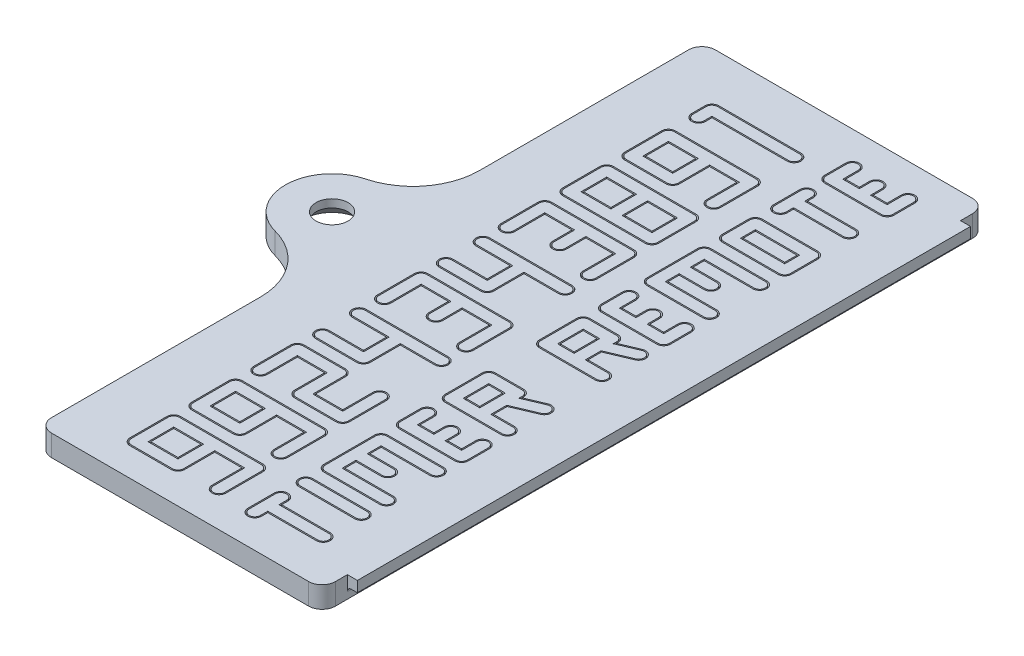
SolidWorks part; units mm, degrees
ref_plane "Front Plane" through (0, 0, 0) normal (0, 0, 1) x (1, 0, 0)
ref_plane "Top Plane" through (0, 0, 0) normal (0, 1, 0) x (1, 0, 0)
ref_plane "Right Plane" through (0, 0, 0) normal (1, 0, 0) x (0, 0, -1)
sketch "Door Plate 1.6 + screw ear (R5 / R3.5) Sketch" plane through (0, 0, 0) normal (0, 1, 0) x (1, 0, 0)
  line L0 (9.35, 15.1) -> (30.65, 15.1)
  line L1 (30.65, 15.1) -> (30.65, 64.9)
  line L2 (30.65, 64.9) -> (9.35, 64.9)
  line L3 (9.35, 64.9) -> (9.35, 48.2236)
  line L4 (9.35, 31.7764) -> (9.35, 15.1)
  arc A0 (9.35, 31.7764) -> (5.6147, 36.6138) centre (4.35, 31.7764) ccw
  arc A1 (5.6147, 36.6138) -> (5.6147, 43.3862) centre (6.5, 40) cw
  arc A2 (5.6147, 43.3862) -> (9.35, 48.2236) centre (4.35, 48.2236) ccw
extrude "Door Plate 1.6 + screw ear (R5 / R3.5)" add sketch "Door Plate 1.6 + screw ear (R5 / R3.5) Sketch" along normal blind 1.6
ref_plane "Hook Flange Plane y0.8" through (0, 0.8, 0) normal (0, 1, 0) x (1, 0, 0)
sketch "Hook Flange 0.75 x 0.8 (inner-face plane) Sketch" plane through (0, 0.8, 0) normal (0, 1, 0) x (1, 0, 0)
  line L0 (30.5, 17) -> (31.4, 17)
  line L1 (31.4, 17) -> (31.4, 63)
  line L2 (31.4, 63) -> (30.5, 63)
  line L3 (30.5, 63) -> (30.5, 17)
extrude "Hook Flange 0.75 x 0.8 (inner-face plane)" add sketch "Hook Flange 0.75 x 0.8 (inner-face plane) Sketch" along normal blind 0.8
sketch "Screw Hole 2.4 (free) Sketch" plane through (0, 0, 0) normal (0, 1, 0) x (1, 0, 0)
  circle A0 centre (6.5, 40) radius 1.2
extrude "Screw Hole 2.4 (free)" cut sketch "Screw Hole 2.4 (free) Sketch" along normal through all
chamfer "Screw CSK 90deg (M2)" distance 1 angle 45 1 edges at (6.5, 0, -38.8)
fillet "Door Corners R1 (print)" radius 1 4 edges at (9.35, 0.8, -64.9) (30.65, 0.8, -64.9) (30.65, 0.8, -15.1) (9.35, 0.8, -15.1)
fillet "Hook Flange Root Fillet R0.3" radius 0.3 1 edges at (30.65, 0.8, -40)
ref_plane "Number Plane y1.6" through (0, 1.6, 0) normal (0, 1, 0) x (1, 0, 0)
sketch "Door Text Slits 9924343891 + TIMER REMOTE (0.84 stroke) Sketch" plane through (0, 1.6, 0) normal (0, 1, 0) x (1, 0, 0)
  line L0 (17.2, 17.22) -> (14.12, 17.22)
  line L1 (13.6, 17.74) -> (13.6, 20.5)
  line L2 (14.12, 21.02) -> (20.28, 21.02)
  line L3 (20.8, 20.5) -> (20.8, 17.74)
  line L4 (19.76, 17.74) -> (19.76, 19.98)
  line L5 (19.76, 19.98) -> (17.72, 19.98)
  line L6 (17.72, 19.98) -> (17.72, 17.74)
  line L7 (13.7, 20.5) -> (13.7, 17.74)
  line L8 (14.12, 17.32) -> (17.2, 17.32)
  line L9 (17.62, 17.74) -> (17.62, 20.08)
  line L10 (17.62, 20.08) -> (19.86, 20.08)
  line L11 (19.86, 20.08) -> (19.86, 17.74)
  line L12 (20.7, 17.74) -> (20.7, 20.5)
  line L13 (20.28, 20.92) -> (14.12, 20.92)
  line L14 (17.2, 21.86) -> (14.12, 21.86)
  line L15 (13.6, 22.38) -> (13.6, 25.14)
  line L16 (14.12, 25.66) -> (20.28, 25.66)
  line L17 (20.8, 25.14) -> (20.8, 22.38)
  line L18 (19.76, 22.38) -> (19.76, 24.62)
  line L19 (19.76, 24.62) -> (17.72, 24.62)
  line L20 (17.72, 24.62) -> (17.72, 22.38)
  line L21 (13.7, 25.14) -> (13.7, 22.38)
  line L22 (14.12, 21.96) -> (17.2, 21.96)
  line L23 (17.62, 22.38) -> (17.62, 24.72)
  line L24 (17.62, 24.72) -> (19.86, 24.72)
  line L25 (19.86, 24.72) -> (19.86, 22.38)
  line L26 (20.7, 22.38) -> (20.7, 25.14)
  line L27 (20.28, 25.56) -> (14.12, 25.56)
  line L28 (20.8, 29.78) -> (20.8, 27.02)
  line L29 (20.28, 26.5) -> (17.2, 26.5)
  line L30 (16.68, 27.02) -> (16.68, 29.26)
  line L31 (16.68, 29.26) -> (14.64, 29.26)
  line L32 (14.64, 29.26) -> (14.64, 27.02)
  line L33 (13.6, 27.02) -> (13.6, 29.78)
  line L34 (14.12, 30.3) -> (17.2, 30.3)
  line L35 (17.72, 29.78) -> (17.72, 27.54)
  line L36 (17.72, 27.54) -> (19.76, 27.54)
  line L37 (19.76, 27.54) -> (19.76, 29.78)
  line L38 (14.54, 29.36) -> (14.54, 27.02)
  line L39 (13.7, 27.02) -> (13.7, 29.78)
  line L40 (14.12, 30.2) -> (17.2, 30.2)
  line L41 (17.62, 29.78) -> (17.62, 27.44)
  line L42 (17.62, 27.44) -> (19.86, 27.44)
  line L43 (19.86, 27.44) -> (19.86, 29.78)
  line L44 (20.7, 29.78) -> (20.7, 27.02)
  line L45 (20.28, 26.6) -> (17.2, 26.6)
  line L46 (16.78, 27.02) -> (16.78, 29.36)
  line L47 (16.78, 29.36) -> (14.54, 29.36)
  line L48 (20.28, 33.9) -> (17.72, 33.9)
  line L49 (17.72, 33.9) -> (17.72, 31.66)
  line L50 (17.2, 31.14) -> (14.12, 31.14)
  line L51 (14.12, 32.18) -> (16.68, 32.18)
  line L52 (16.68, 32.18) -> (16.68, 33.9)
  line L53 (16.68, 33.9) -> (14.12, 33.9)
  line L54 (14.12, 34.94) -> (20.28, 34.94)
  line L55 (17.62, 31.66) -> (17.62, 34)
  line L56 (17.62, 34) -> (20.28, 34)
  line L57 (20.28, 34.84) -> (14.12, 34.84)
  line L58 (14.12, 34) -> (16.78, 34)
  line L59 (16.78, 34) -> (16.78, 32.08)
  line L60 (16.78, 32.08) -> (14.12, 32.08)
  line L61 (14.12, 31.24) -> (17.2, 31.24)
  line L62 (19.76, 36.3) -> (19.76, 38.54)
  line L63 (19.76, 38.54) -> (17.72, 38.54)
  line L64 (17.72, 38.54) -> (17.72, 37.1)
  line L65 (16.68, 37.1) -> (16.68, 38.54)
  line L66 (16.68, 38.54) -> (14.64, 38.54)
  line L67 (14.64, 38.54) -> (14.64, 36.3)
  line L68 (13.6, 36.3) -> (13.6, 39.06)
  line L69 (14.12, 39.58) -> (20.28, 39.58)
  line L70 (20.8, 39.06) -> (20.8, 36.3)
  line L71 (13.7, 36.3) -> (13.7, 39.06)
  line L72 (14.12, 39.48) -> (20.28, 39.48)
  line L73 (20.7, 39.06) -> (20.7, 36.3)
  line L74 (19.86, 36.3) -> (19.86, 38.64)
  line L75 (19.86, 38.64) -> (17.62, 38.64)
  line L76 (17.62, 38.64) -> (17.62, 37.1)
  line L77 (16.78, 37.1) -> (16.78, 38.64)
  line L78 (16.78, 38.64) -> (14.54, 38.64)
  line L79 (14.54, 38.64) -> (14.54, 36.3)
  line L80 (20.28, 43.18) -> (17.72, 43.18)
  line L81 (17.72, 43.18) -> (17.72, 40.94)
  line L82 (17.2, 40.42) -> (14.12, 40.42)
  line L83 (14.12, 41.46) -> (16.68, 41.46)
  line L84 (16.68, 41.46) -> (16.68, 43.18)
  line L85 (16.68, 43.18) -> (14.12, 43.18)
  line L86 (14.12, 44.22) -> (20.28, 44.22)
  line L87 (17.62, 40.94) -> (17.62, 43.28)
  line L88 (17.62, 43.28) -> (20.28, 43.28)
  line L89 (20.28, 44.12) -> (14.12, 44.12)
  line L90 (14.12, 43.28) -> (16.78, 43.28)
  line L91 (16.78, 43.28) -> (16.78, 41.36)
  line L92 (16.78, 41.36) -> (14.12, 41.36)
  line L93 (14.12, 40.52) -> (17.2, 40.52)
  line L94 (19.76, 45.58) -> (19.76, 47.82)
  line L95 (19.76, 47.82) -> (17.72, 47.82)
  line L96 (17.72, 47.82) -> (17.72, 46.38)
  line L97 (16.68, 46.38) -> (16.68, 47.82)
  line L98 (16.68, 47.82) -> (14.64, 47.82)
  line L99 (14.64, 47.82) -> (14.64, 45.58)
  line L100 (13.6, 45.58) -> (13.6, 48.34)
  line L101 (14.12, 48.86) -> (20.28, 48.86)
  line L102 (20.8, 48.34) -> (20.8, 45.58)
  line L103 (13.7, 45.58) -> (13.7, 48.34)
  line L104 (14.12, 48.76) -> (20.28, 48.76)
  line L105 (20.7, 48.34) -> (20.7, 45.58)
  line L106 (19.86, 45.58) -> (19.86, 47.92)
  line L107 (19.86, 47.92) -> (17.62, 47.92)
  line L108 (17.62, 47.92) -> (17.62, 46.38)
  line L109 (16.78, 46.38) -> (16.78, 47.92)
  line L110 (16.78, 47.92) -> (14.54, 47.92)
  line L111 (14.54, 47.92) -> (14.54, 45.58)
  line L112 (20.8, 52.98) -> (20.8, 50.22)
  line L113 (20.28, 49.7) -> (14.12, 49.7)
  line L114 (13.6, 50.22) -> (13.6, 52.98)
  line L115 (14.12, 53.5) -> (20.28, 53.5)
  line L116 (20.7, 50.22) -> (20.7, 52.98)
  line L117 (20.28, 53.4) -> (14.12, 53.4)
  line L118 (13.7, 52.98) -> (13.7, 50.22)
  line L119 (14.12, 49.8) -> (20.28, 49.8)
  line L120 (17.2, 54.34) -> (14.12, 54.34)
  line L121 (13.6, 54.86) -> (13.6, 57.62)
  line L122 (14.12, 58.14) -> (20.28, 58.14)
  line L123 (20.8, 57.62) -> (20.8, 54.86)
  line L124 (19.76, 54.86) -> (19.76, 57.1)
  line L125 (19.76, 57.1) -> (17.72, 57.1)
  line L126 (17.72, 57.1) -> (17.72, 54.86)
  line L127 (13.7, 57.62) -> (13.7, 54.86)
  line L128 (14.12, 54.44) -> (17.2, 54.44)
  line L129 (17.62, 54.86) -> (17.62, 57.2)
  line L130 (17.62, 57.2) -> (19.86, 57.2)
  line L131 (19.86, 57.2) -> (19.86, 54.86)
  line L132 (20.7, 54.86) -> (20.7, 57.62)
  line L133 (20.28, 58.04) -> (14.12, 58.04)
  line L134 (20.28, 60.36) -> (14.64, 60.36)
  line L135 (14.64, 60.36) -> (14.64, 59.88)
  line L136 (13.6, 59.88) -> (13.6, 60.88)
  line L137 (14.12, 61.4) -> (20.28, 61.4)
  line L138 (14.54, 60.46) -> (14.54, 59.88)
  line L139 (13.7, 59.88) -> (13.7, 60.88)
  line L140 (14.12, 61.3) -> (20.28, 61.3)
  line L141 (20.28, 60.46) -> (14.54, 60.46)
  line L142 (23.64, 19.08) -> (27.28, 19.08)
  line L143 (27.28, 18.04) -> (23.64, 18.04)
  line L144 (23.64, 18.04) -> (23.64, 17.58)
  line L145 (22.6, 17.58) -> (22.6, 19.54)
  line L146 (23.64, 19.54) -> (23.64, 19.08)
  line L147 (22.7, 17.58) -> (22.7, 19.54)
  line L148 (23.54, 19.54) -> (23.54, 18.98)
  line L149 (23.54, 18.98) -> (27.28, 18.98)
  line L150 (27.28, 18.14) -> (23.54, 18.14)
  line L151 (23.54, 18.14) -> (23.54, 17.58)
  line L152 (27.28, 20.9) -> (23.12, 20.9)
  line L153 (23.12, 21.94) -> (27.28, 21.94)
  line L154 (27.28, 21) -> (23.12, 21)
  line L155 (23.12, 21.84) -> (27.28, 21.84)
  line L156 (27.28, 26.54) -> (23.64, 26.54)
  line L157 (23.64, 26.54) -> (23.64, 25.7)
  line L158 (23.64, 25.7) -> (25.5, 25.7)
  line L159 (25.5, 24.66) -> (23.64, 24.66)
  line L160 (23.64, 24.66) -> (23.64, 23.82)
  line L161 (23.64, 23.82) -> (27.28, 23.82)
  line L162 (27.28, 22.78) -> (23.12, 22.78)
  line L163 (22.6, 23.3) -> (22.6, 27.06)
  line L164 (23.12, 27.58) -> (27.28, 27.58)
  line L165 (27.28, 22.88) -> (23.12, 22.88)
  line L166 (22.7, 23.3) -> (22.7, 27.06)
  line L167 (23.12, 27.48) -> (27.28, 27.48)
  line L168 (27.28, 26.64) -> (23.54, 26.64)
  line L169 (23.54, 26.64) -> (23.54, 25.6)
  line L170 (23.54, 25.6) -> (25.5, 25.6)
  line L171 (25.5, 24.76) -> (23.54, 24.76)
  line L172 (23.54, 24.76) -> (23.54, 23.72)
  line L173 (23.54, 23.72) -> (27.28, 23.72)
  line L174 (26.76, 29.46) -> (26.76, 30.5)
  line L175 (27.8, 30.5) -> (27.8, 28.94)
  line L176 (27.28, 28.42) -> (23.12, 28.42)
  line L177 (22.6, 28.94) -> (22.6, 30.5)
  line L178 (23.64, 30.5) -> (23.64, 29.46)
  line L179 (23.64, 29.46) -> (24.68, 29.46)
  line L180 (24.68, 29.46) -> (24.68, 30.2)
  line L181 (25.72, 30.2) -> (25.72, 29.46)
  line L182 (25.72, 29.46) -> (26.76, 29.46)
  line L183 (23.12, 28.52) -> (27.28, 28.52)
  line L184 (27.7, 28.94) -> (27.7, 30.5)
  line L185 (26.86, 30.5) -> (26.86, 29.36)
  line L186 (26.86, 29.36) -> (25.62, 29.36)
  line L187 (25.62, 29.36) -> (25.62, 30.2)
  line L188 (24.78, 30.2) -> (24.78, 29.36)
  line L189 (24.78, 29.36) -> (23.54, 29.36)
  line L190 (23.54, 29.36) -> (23.54, 30.5)
  line L191 (22.7, 30.5) -> (22.7, 28.94)
  line L192 (25.72, 35.14) -> (25.72, 35.0446)
  line L193 (25.72, 35.0446) -> (27.0774, 35.6189)
  line L194 (27.4826, 34.6611) -> (25.72, 33.9154)
  line L195 (25.72, 33.9154) -> (25.72, 32.9)
  line L196 (25.72, 32.9) -> (27.28, 32.9)
  line L197 (27.28, 31.86) -> (23.12, 31.86)
  line L198 (22.6, 32.38) -> (22.6, 35.14)
  line L199 (23.12, 35.66) -> (25.2, 35.66)
  line L200 (27.28, 31.96) -> (23.12, 31.96)
  line L201 (22.7, 32.38) -> (22.7, 35.14)
  line L202 (23.12, 35.56) -> (25.2, 35.56)
  line L203 (25.62, 35.14) -> (25.62, 34.8937)
  line L204 (25.62, 34.8937) -> (27.1164, 35.5268)
  line L205 (27.4436, 34.7532) -> (25.62, 33.9817)
  line L206 (25.62, 33.9817) -> (25.62, 32.8)
  line L207 (25.62, 32.8) -> (27.28, 32.8)
  line L208 (25.72, 42.22) -> (25.72, 42.1246)
  line L209 (25.72, 42.1246) -> (27.0774, 42.6989)
  line L210 (27.4826, 41.7411) -> (25.72, 40.9954)
  line L211 (25.72, 40.9954) -> (25.72, 39.98)
  line L212 (25.72, 39.98) -> (27.28, 39.98)
  line L213 (27.28, 38.94) -> (23.12, 38.94)
  line L214 (22.6, 39.46) -> (22.6, 42.22)
  line L215 (23.12, 42.74) -> (25.2, 42.74)
  line L216 (27.28, 39.04) -> (23.12, 39.04)
  line L217 (22.7, 39.46) -> (22.7, 42.22)
  line L218 (23.12, 42.64) -> (25.2, 42.64)
  line L219 (25.62, 42.22) -> (25.62, 41.9737)
  line L220 (25.62, 41.9737) -> (27.1164, 42.6068)
  line L221 (27.4436, 41.8332) -> (25.62, 41.0617)
  line L222 (25.62, 41.0617) -> (25.62, 39.88)
  line L223 (25.62, 39.88) -> (27.28, 39.88)
  line L224 (26.76, 44.62) -> (26.76, 45.66)
  line L225 (27.8, 45.66) -> (27.8, 44.1)
  line L226 (27.28, 43.58) -> (23.12, 43.58)
  line L227 (22.6, 44.1) -> (22.6, 45.66)
  line L228 (23.64, 45.66) -> (23.64, 44.62)
  line L229 (23.64, 44.62) -> (24.68, 44.62)
  line L230 (24.68, 44.62) -> (24.68, 45.36)
  line L231 (25.72, 45.36) -> (25.72, 44.62)
  line L232 (25.72, 44.62) -> (26.76, 44.62)
  line L233 (23.12, 43.68) -> (27.28, 43.68)
  line L234 (27.7, 44.1) -> (27.7, 45.66)
  line L235 (26.86, 45.66) -> (26.86, 44.52)
  line L236 (26.86, 44.52) -> (25.62, 44.52)
  line L237 (25.62, 44.52) -> (25.62, 45.36)
  line L238 (24.78, 45.36) -> (24.78, 44.52)
  line L239 (24.78, 44.52) -> (23.54, 44.52)
  line L240 (23.54, 44.52) -> (23.54, 45.66)
  line L241 (22.7, 45.66) -> (22.7, 44.1)
  line L242 (27.28, 50.78) -> (23.64, 50.78)
  line L243 (23.64, 50.78) -> (23.64, 49.94)
  line L244 (23.64, 49.94) -> (25.5, 49.94)
  line L245 (25.5, 48.9) -> (23.64, 48.9)
  line L246 (23.64, 48.9) -> (23.64, 48.06)
  line L247 (23.64, 48.06) -> (27.28, 48.06)
  line L248 (27.28, 47.02) -> (23.12, 47.02)
  line L249 (22.6, 47.54) -> (22.6, 51.3)
  line L250 (23.12, 51.82) -> (27.28, 51.82)
  line L251 (27.28, 47.12) -> (23.12, 47.12)
  line L252 (22.7, 47.54) -> (22.7, 51.3)
  line L253 (23.12, 51.72) -> (27.28, 51.72)
  line L254 (27.28, 50.88) -> (23.54, 50.88)
  line L255 (23.54, 50.88) -> (23.54, 49.84)
  line L256 (23.54, 49.84) -> (25.5, 49.84)
  line L257 (25.5, 49) -> (23.54, 49)
  line L258 (23.54, 49) -> (23.54, 47.96)
  line L259 (23.54, 47.96) -> (27.28, 47.96)
  line L260 (27.8, 55.14) -> (27.8, 53.18)
  line L261 (27.28, 52.66) -> (23.12, 52.66)
  line L262 (22.6, 53.18) -> (22.6, 55.14)
  line L263 (23.12, 55.66) -> (27.28, 55.66)
  line L264 (27.7, 53.18) -> (27.7, 55.14)
  line L265 (27.28, 55.56) -> (23.12, 55.56)
  line L266 (22.7, 55.14) -> (22.7, 53.18)
  line L267 (23.12, 52.76) -> (27.28, 52.76)
  line L268 (23.64, 58.52) -> (27.28, 58.52)
  line L269 (27.28, 57.48) -> (23.64, 57.48)
  line L270 (23.64, 57.48) -> (23.64, 57.02)
  line L271 (22.6, 57.02) -> (22.6, 58.98)
  line L272 (23.64, 58.98) -> (23.64, 58.52)
  line L273 (22.7, 57.02) -> (22.7, 58.98)
  line L274 (23.54, 58.98) -> (23.54, 58.42)
  line L275 (23.54, 58.42) -> (27.28, 58.42)
  line L276 (27.28, 57.58) -> (23.54, 57.58)
  line L277 (23.54, 57.58) -> (23.54, 57.02)
  line L278 (26.76, 61.38) -> (26.76, 62.42)
  line L279 (27.8, 62.42) -> (27.8, 60.86)
  line L280 (27.28, 60.34) -> (23.12, 60.34)
  line L281 (22.6, 60.86) -> (22.6, 62.42)
  line L282 (23.64, 62.42) -> (23.64, 61.38)
  line L283 (23.64, 61.38) -> (24.68, 61.38)
  line L284 (24.68, 61.38) -> (24.68, 62.12)
  line L285 (25.72, 62.12) -> (25.72, 61.38)
  line L286 (25.72, 61.38) -> (26.76, 61.38)
  line L287 (23.12, 60.44) -> (27.28, 60.44)
  line L288 (27.7, 60.86) -> (27.7, 62.42)
  line L289 (26.86, 62.42) -> (26.86, 61.28)
  line L290 (26.86, 61.28) -> (25.62, 61.28)
  line L291 (25.62, 61.28) -> (25.62, 62.12)
  line L292 (24.78, 62.12) -> (24.78, 61.28)
  line L293 (24.78, 61.28) -> (23.54, 61.28)
  line L294 (23.54, 61.28) -> (23.54, 62.42)
  line L295 (22.7, 62.42) -> (22.7, 60.86)
  arc A0 (17.72, 17.74) -> (17.2, 17.22) centre (17.2, 17.74) cw
  arc A1 (14.12, 17.22) -> (13.6, 17.74) centre (14.12, 17.74) cw
  arc A2 (13.6, 20.5) -> (14.12, 21.02) centre (14.12, 20.5) cw
  arc A3 (20.28, 21.02) -> (20.8, 20.5) centre (20.28, 20.5) cw
  arc A4 (20.8, 17.74) -> (19.76, 17.74) centre (20.28, 17.74) cw
  arc A5 (14.12, 20.92) -> (13.7, 20.5) centre (14.12, 20.5) ccw
  arc A6 (13.7, 17.74) -> (14.12, 17.32) centre (14.12, 17.74) ccw
  arc A7 (17.2, 17.32) -> (17.62, 17.74) centre (17.2, 17.74) ccw
  arc A8 (19.86, 17.74) -> (20.7, 17.74) centre (20.28, 17.74) ccw
  arc A9 (20.7, 20.5) -> (20.28, 20.92) centre (20.28, 20.5) ccw
  arc A10 (17.72, 22.38) -> (17.2, 21.86) centre (17.2, 22.38) cw
  arc A11 (14.12, 21.86) -> (13.6, 22.38) centre (14.12, 22.38) cw
  arc A12 (13.6, 25.14) -> (14.12, 25.66) centre (14.12, 25.14) cw
  arc A13 (20.28, 25.66) -> (20.8, 25.14) centre (20.28, 25.14) cw
  arc A14 (20.8, 22.38) -> (19.76, 22.38) centre (20.28, 22.38) cw
  arc A15 (14.12, 25.56) -> (13.7, 25.14) centre (14.12, 25.14) ccw
  arc A16 (13.7, 22.38) -> (14.12, 21.96) centre (14.12, 22.38) ccw
  arc A17 (17.2, 21.96) -> (17.62, 22.38) centre (17.2, 22.38) ccw
  arc A18 (19.86, 22.38) -> (20.7, 22.38) centre (20.28, 22.38) ccw
  arc A19 (20.7, 25.14) -> (20.28, 25.56) centre (20.28, 25.14) ccw
  arc A20 (19.76, 29.78) -> (20.8, 29.78) centre (20.28, 29.78) cw
  arc A21 (20.8, 27.02) -> (20.28, 26.5) centre (20.28, 27.02) cw
  arc A22 (17.2, 26.5) -> (16.68, 27.02) centre (17.2, 27.02) cw
  arc A23 (14.64, 27.02) -> (13.6, 27.02) centre (14.12, 27.02) cw
  arc A24 (13.6, 29.78) -> (14.12, 30.3) centre (14.12, 29.78) cw
  arc A25 (17.2, 30.3) -> (17.72, 29.78) centre (17.2, 29.78) cw
  arc A26 (14.54, 27.02) -> (13.7, 27.02) centre (14.12, 27.02) cw
  arc A27 (13.7, 29.78) -> (14.12, 30.2) centre (14.12, 29.78) cw
  arc A28 (17.2, 30.2) -> (17.62, 29.78) centre (17.2, 29.78) cw
  arc A29 (19.86, 29.78) -> (20.7, 29.78) centre (20.28, 29.78) cw
  arc A30 (20.7, 27.02) -> (20.28, 26.6) centre (20.28, 27.02) cw
  arc A31 (17.2, 26.6) -> (16.78, 27.02) centre (17.2, 27.02) cw
  arc A32 (20.28, 34.94) -> (20.8, 34.42) centre (20.28, 34.42) cw
  arc A33 (20.8, 34.42) -> (20.28, 33.9) centre (20.28, 34.42) cw
  arc A34 (17.72, 31.66) -> (17.2, 31.14) centre (17.2, 31.66) cw
  arc A35 (14.12, 31.14) -> (14.12, 32.18) centre (14.12, 31.66) cw
  arc A36 (14.12, 33.9) -> (14.12, 34.94) centre (14.12, 34.42) cw
  arc A37 (17.2, 31.24) -> (17.62, 31.66) centre (17.2, 31.66) ccw
  arc A38 (20.28, 34) -> (20.7, 34.42) centre (20.28, 34.42) ccw
  arc A39 (20.7, 34.42) -> (20.28, 34.84) centre (20.28, 34.42) ccw
  arc A40 (14.12, 34.84) -> (14.12, 34) centre (14.12, 34.42) ccw
  arc A41 (14.12, 32.08) -> (14.12, 31.24) centre (14.12, 31.66) ccw
  arc A42 (17.72, 37.1) -> (16.68, 37.1) centre (17.2, 37.1) cw
  arc A43 (14.64, 36.3) -> (13.6, 36.3) centre (14.12, 36.3) cw
  arc A44 (13.6, 39.06) -> (14.12, 39.58) centre (14.12, 39.06) cw
  arc A45 (20.28, 39.58) -> (20.8, 39.06) centre (20.28, 39.06) cw
  arc A46 (20.8, 36.3) -> (19.76, 36.3) centre (20.28, 36.3) cw
  arc A47 (14.54, 36.3) -> (13.7, 36.3) centre (14.12, 36.3) cw
  arc A48 (13.7, 39.06) -> (14.12, 39.48) centre (14.12, 39.06) cw
  arc A49 (20.28, 39.48) -> (20.7, 39.06) centre (20.28, 39.06) cw
  arc A50 (20.7, 36.3) -> (19.86, 36.3) centre (20.28, 36.3) cw
  arc A51 (17.62, 37.1) -> (16.78, 37.1) centre (17.2, 37.1) cw
  arc A52 (20.28, 44.22) -> (20.8, 43.7) centre (20.28, 43.7) cw
  arc A53 (20.8, 43.7) -> (20.28, 43.18) centre (20.28, 43.7) cw
  arc A54 (17.72, 40.94) -> (17.2, 40.42) centre (17.2, 40.94) cw
  arc A55 (14.12, 40.42) -> (14.12, 41.46) centre (14.12, 40.94) cw
  arc A56 (14.12, 43.18) -> (14.12, 44.22) centre (14.12, 43.7) cw
  arc A57 (17.2, 40.52) -> (17.62, 40.94) centre (17.2, 40.94) ccw
  arc A58 (20.28, 43.28) -> (20.7, 43.7) centre (20.28, 43.7) ccw
  arc A59 (20.7, 43.7) -> (20.28, 44.12) centre (20.28, 43.7) ccw
  arc A60 (14.12, 44.12) -> (14.12, 43.28) centre (14.12, 43.7) ccw
  arc A61 (14.12, 41.36) -> (14.12, 40.52) centre (14.12, 40.94) ccw
  arc A62 (17.72, 46.38) -> (16.68, 46.38) centre (17.2, 46.38) cw
  arc A63 (14.64, 45.58) -> (13.6, 45.58) centre (14.12, 45.58) cw
  arc A64 (13.6, 48.34) -> (14.12, 48.86) centre (14.12, 48.34) cw
  arc A65 (20.28, 48.86) -> (20.8, 48.34) centre (20.28, 48.34) cw
  arc A66 (20.8, 45.58) -> (19.76, 45.58) centre (20.28, 45.58) cw
  arc A67 (14.54, 45.58) -> (13.7, 45.58) centre (14.12, 45.58) cw
  arc A68 (13.7, 48.34) -> (14.12, 48.76) centre (14.12, 48.34) cw
  arc A69 (20.28, 48.76) -> (20.7, 48.34) centre (20.28, 48.34) cw
  arc A70 (20.7, 45.58) -> (19.86, 45.58) centre (20.28, 45.58) cw
  arc A71 (17.62, 46.38) -> (16.78, 46.38) centre (17.2, 46.38) cw
  arc A72 (20.28, 53.5) -> (20.8, 52.98) centre (20.28, 52.98) cw
  arc A73 (20.8, 50.22) -> (20.28, 49.7) centre (20.28, 50.22) cw
  arc A74 (14.12, 49.7) -> (13.6, 50.22) centre (14.12, 50.22) cw
  arc A75 (13.6, 52.98) -> (14.12, 53.5) centre (14.12, 52.98) cw
  arc A76 (20.28, 49.8) -> (20.7, 50.22) centre (20.28, 50.22) ccw
  arc A77 (20.7, 52.98) -> (20.28, 53.4) centre (20.28, 52.98) ccw
  arc A78 (14.12, 53.4) -> (13.7, 52.98) centre (14.12, 52.98) ccw
  arc A79 (13.7, 50.22) -> (14.12, 49.8) centre (14.12, 50.22) ccw
  arc A80 (17.72, 54.86) -> (17.2, 54.34) centre (17.2, 54.86) cw
  arc A81 (14.12, 54.34) -> (13.6, 54.86) centre (14.12, 54.86) cw
  arc A82 (13.6, 57.62) -> (14.12, 58.14) centre (14.12, 57.62) cw
  arc A83 (20.28, 58.14) -> (20.8, 57.62) centre (20.28, 57.62) cw
  arc A84 (20.8, 54.86) -> (19.76, 54.86) centre (20.28, 54.86) cw
  arc A85 (14.12, 58.04) -> (13.7, 57.62) centre (14.12, 57.62) ccw
  arc A86 (13.7, 54.86) -> (14.12, 54.44) centre (14.12, 54.86) ccw
  arc A87 (17.2, 54.44) -> (17.62, 54.86) centre (17.2, 54.86) ccw
  arc A88 (19.86, 54.86) -> (20.7, 54.86) centre (20.28, 54.86) ccw
  arc A89 (20.7, 57.62) -> (20.28, 58.04) centre (20.28, 57.62) ccw
  arc A90 (20.28, 61.4) -> (20.8, 60.88) centre (20.28, 60.88) cw
  arc A91 (20.8, 60.88) -> (20.28, 60.36) centre (20.28, 60.88) cw
  arc A92 (14.64, 59.88) -> (13.6, 59.88) centre (14.12, 59.88) cw
  arc A93 (13.6, 60.88) -> (14.12, 61.4) centre (14.12, 60.88) cw
  arc A94 (14.54, 59.88) -> (13.7, 59.88) centre (14.12, 59.88) cw
  arc A95 (13.7, 60.88) -> (14.12, 61.3) centre (14.12, 60.88) cw
  arc A96 (20.28, 61.3) -> (20.7, 60.88) centre (20.28, 60.88) cw
  arc A97 (20.7, 60.88) -> (20.28, 60.46) centre (20.28, 60.88) cw
  arc A98 (27.28, 19.08) -> (27.8, 18.56) centre (27.28, 18.56) cw
  arc A99 (27.8, 18.56) -> (27.28, 18.04) centre (27.28, 18.56) cw
  arc A100 (23.64, 17.58) -> (22.6, 17.58) centre (23.12, 17.58) cw
  arc A101 (22.6, 19.54) -> (23.64, 19.54) centre (23.12, 19.54) cw
  arc A102 (23.54, 17.58) -> (22.7, 17.58) centre (23.12, 17.58) cw
  arc A103 (22.7, 19.54) -> (23.54, 19.54) centre (23.12, 19.54) cw
  arc A104 (27.28, 18.98) -> (27.7, 18.56) centre (27.28, 18.56) cw
  arc A105 (27.7, 18.56) -> (27.28, 18.14) centre (27.28, 18.56) cw
  arc A106 (27.28, 21.94) -> (27.8, 21.42) centre (27.28, 21.42) cw
  arc A107 (27.8, 21.42) -> (27.28, 20.9) centre (27.28, 21.42) cw
  arc A108 (23.12, 20.9) -> (23.12, 21.94) centre (23.12, 21.42) cw
  arc A109 (23.12, 21) -> (23.12, 21.84) centre (23.12, 21.42) cw
  arc A110 (27.28, 21.84) -> (27.7, 21.42) centre (27.28, 21.42) cw
  arc A111 (27.7, 21.42) -> (27.28, 21) centre (27.28, 21.42) cw
  arc A112 (27.8, 27.06) -> (27.28, 26.54) centre (27.28, 27.06) cw
  arc A113 (25.5, 25.7) -> (26.02, 25.18) centre (25.5, 25.18) cw
  arc A114 (26.02, 25.18) -> (25.5, 24.66) centre (25.5, 25.18) cw
  arc A115 (27.28, 23.82) -> (27.8, 23.3) centre (27.28, 23.3) cw
  arc A116 (27.8, 23.3) -> (27.28, 22.78) centre (27.28, 23.3) cw
  arc A117 (23.12, 22.78) -> (22.6, 23.3) centre (23.12, 23.3) cw
  arc A118 (22.6, 27.06) -> (23.12, 27.58) centre (23.12, 27.06) cw
  arc A119 (27.28, 27.58) -> (27.8, 27.06) centre (27.28, 27.06) cw
  arc A120 (27.28, 23.72) -> (27.7, 23.3) centre (27.28, 23.3) cw
  arc A121 (27.7, 23.3) -> (27.28, 22.88) centre (27.28, 23.3) cw
  arc A122 (23.12, 22.88) -> (22.7, 23.3) centre (23.12, 23.3) cw
  arc A123 (22.7, 27.06) -> (23.12, 27.48) centre (23.12, 27.06) cw
  arc A124 (27.28, 27.48) -> (27.7, 27.06) centre (27.28, 27.06) cw
  arc A125 (27.7, 27.06) -> (27.28, 26.64) centre (27.28, 27.06) cw
  arc A126 (25.5, 25.6) -> (25.92, 25.18) centre (25.5, 25.18) cw
  arc A127 (25.92, 25.18) -> (25.5, 24.76) centre (25.5, 25.18) cw
  arc A128 (26.76, 30.5) -> (27.8, 30.5) centre (27.28, 30.5) cw
  arc A129 (27.8, 28.94) -> (27.28, 28.42) centre (27.28, 28.94) cw
  arc A130 (23.12, 28.42) -> (22.6, 28.94) centre (23.12, 28.94) cw
  arc A131 (22.6, 30.5) -> (23.64, 30.5) centre (23.12, 30.5) cw
  arc A132 (24.68, 30.2) -> (25.72, 30.2) centre (25.2, 30.2) cw
  arc A133 (22.7, 28.94) -> (23.12, 28.52) centre (23.12, 28.94) ccw
  arc A134 (27.28, 28.52) -> (27.7, 28.94) centre (27.28, 28.94) ccw
  arc A135 (27.7, 30.5) -> (26.86, 30.5) centre (27.28, 30.5) ccw
  arc A136 (25.62, 30.2) -> (24.78, 30.2) centre (25.2, 30.2) ccw
  arc A137 (23.54, 30.5) -> (22.7, 30.5) centre (23.12, 30.5) ccw
  arc A138 (25.2, 35.66) -> (25.72, 35.14) centre (25.2, 35.14) cw
  arc A139 (27.0774, 35.6189) -> (27.8, 35.14) centre (27.28, 35.14) cw
  arc A140 (27.8, 35.14) -> (27.4826, 34.6611) centre (27.28, 35.14) cw
  arc A141 (27.28, 32.9) -> (27.8, 32.38) centre (27.28, 32.38) cw
  arc A142 (27.8, 32.38) -> (27.28, 31.86) centre (27.28, 32.38) cw
  arc A143 (23.12, 31.86) -> (22.6, 32.38) centre (23.12, 32.38) cw
  arc A144 (22.6, 35.14) -> (23.12, 35.66) centre (23.12, 35.14) cw
  arc A145 (27.28, 32.8) -> (27.7, 32.38) centre (27.28, 32.38) cw
  arc A146 (27.7, 32.38) -> (27.28, 31.96) centre (27.28, 32.38) cw
  arc A147 (23.12, 31.96) -> (22.7, 32.38) centre (23.12, 32.38) cw
  arc A148 (22.7, 35.14) -> (23.12, 35.56) centre (23.12, 35.14) cw
  arc A149 (25.2, 35.56) -> (25.62, 35.14) centre (25.2, 35.14) cw
  arc A150 (27.1164, 35.5268) -> (27.7, 35.14) centre (27.28, 35.14) cw
  arc A151 (27.7, 35.14) -> (27.4436, 34.7532) centre (27.28, 35.14) cw
  arc A152 (25.2, 42.74) -> (25.72, 42.22) centre (25.2, 42.22) cw
  arc A153 (27.0774, 42.6989) -> (27.8, 42.22) centre (27.28, 42.22) cw
  arc A154 (27.8, 42.22) -> (27.4826, 41.7411) centre (27.28, 42.22) cw
  arc A155 (27.28, 39.98) -> (27.8, 39.46) centre (27.28, 39.46) cw
  arc A156 (27.8, 39.46) -> (27.28, 38.94) centre (27.28, 39.46) cw
  arc A157 (23.12, 38.94) -> (22.6, 39.46) centre (23.12, 39.46) cw
  arc A158 (22.6, 42.22) -> (23.12, 42.74) centre (23.12, 42.22) cw
  arc A159 (27.28, 39.88) -> (27.7, 39.46) centre (27.28, 39.46) cw
  arc A160 (27.7, 39.46) -> (27.28, 39.04) centre (27.28, 39.46) cw
  arc A161 (23.12, 39.04) -> (22.7, 39.46) centre (23.12, 39.46) cw
  arc A162 (22.7, 42.22) -> (23.12, 42.64) centre (23.12, 42.22) cw
  arc A163 (25.2, 42.64) -> (25.62, 42.22) centre (25.2, 42.22) cw
  arc A164 (27.1164, 42.6068) -> (27.7, 42.22) centre (27.28, 42.22) cw
  arc A165 (27.7, 42.22) -> (27.4436, 41.8332) centre (27.28, 42.22) cw
  arc A166 (26.76, 45.66) -> (27.8, 45.66) centre (27.28, 45.66) cw
  arc A167 (27.8, 44.1) -> (27.28, 43.58) centre (27.28, 44.1) cw
  arc A168 (23.12, 43.58) -> (22.6, 44.1) centre (23.12, 44.1) cw
  arc A169 (22.6, 45.66) -> (23.64, 45.66) centre (23.12, 45.66) cw
  arc A170 (24.68, 45.36) -> (25.72, 45.36) centre (25.2, 45.36) cw
  arc A171 (22.7, 44.1) -> (23.12, 43.68) centre (23.12, 44.1) ccw
  arc A172 (27.28, 43.68) -> (27.7, 44.1) centre (27.28, 44.1) ccw
  arc A173 (27.7, 45.66) -> (26.86, 45.66) centre (27.28, 45.66) ccw
  arc A174 (25.62, 45.36) -> (24.78, 45.36) centre (25.2, 45.36) ccw
  arc A175 (23.54, 45.66) -> (22.7, 45.66) centre (23.12, 45.66) ccw
  arc A176 (27.8, 51.3) -> (27.28, 50.78) centre (27.28, 51.3) cw
  arc A177 (25.5, 49.94) -> (26.02, 49.42) centre (25.5, 49.42) cw
  arc A178 (26.02, 49.42) -> (25.5, 48.9) centre (25.5, 49.42) cw
  arc A179 (27.28, 48.06) -> (27.8, 47.54) centre (27.28, 47.54) cw
  arc A180 (27.8, 47.54) -> (27.28, 47.02) centre (27.28, 47.54) cw
  arc A181 (23.12, 47.02) -> (22.6, 47.54) centre (23.12, 47.54) cw
  arc A182 (22.6, 51.3) -> (23.12, 51.82) centre (23.12, 51.3) cw
  arc A183 (27.28, 51.82) -> (27.8, 51.3) centre (27.28, 51.3) cw
  arc A184 (27.28, 47.96) -> (27.7, 47.54) centre (27.28, 47.54) cw
  arc A185 (27.7, 47.54) -> (27.28, 47.12) centre (27.28, 47.54) cw
  arc A186 (23.12, 47.12) -> (22.7, 47.54) centre (23.12, 47.54) cw
  arc A187 (22.7, 51.3) -> (23.12, 51.72) centre (23.12, 51.3) cw
  arc A188 (27.28, 51.72) -> (27.7, 51.3) centre (27.28, 51.3) cw
  arc A189 (27.7, 51.3) -> (27.28, 50.88) centre (27.28, 51.3) cw
  arc A190 (25.5, 49.84) -> (25.92, 49.42) centre (25.5, 49.42) cw
  arc A191 (25.92, 49.42) -> (25.5, 49) centre (25.5, 49.42) cw
  arc A192 (27.28, 55.66) -> (27.8, 55.14) centre (27.28, 55.14) cw
  arc A193 (27.8, 53.18) -> (27.28, 52.66) centre (27.28, 53.18) cw
  arc A194 (23.12, 52.66) -> (22.6, 53.18) centre (23.12, 53.18) cw
  arc A195 (22.6, 55.14) -> (23.12, 55.66) centre (23.12, 55.14) cw
  arc A196 (27.28, 52.76) -> (27.7, 53.18) centre (27.28, 53.18) ccw
  arc A197 (27.7, 55.14) -> (27.28, 55.56) centre (27.28, 55.14) ccw
  arc A198 (23.12, 55.56) -> (22.7, 55.14) centre (23.12, 55.14) ccw
  arc A199 (22.7, 53.18) -> (23.12, 52.76) centre (23.12, 53.18) ccw
  arc A200 (27.28, 58.52) -> (27.8, 58) centre (27.28, 58) cw
  arc A201 (27.8, 58) -> (27.28, 57.48) centre (27.28, 58) cw
  arc A202 (23.64, 57.02) -> (22.6, 57.02) centre (23.12, 57.02) cw
  arc A203 (22.6, 58.98) -> (23.64, 58.98) centre (23.12, 58.98) cw
  arc A204 (23.54, 57.02) -> (22.7, 57.02) centre (23.12, 57.02) cw
  arc A205 (22.7, 58.98) -> (23.54, 58.98) centre (23.12, 58.98) cw
  arc A206 (27.28, 58.42) -> (27.7, 58) centre (27.28, 58) cw
  arc A207 (27.7, 58) -> (27.28, 57.58) centre (27.28, 58) cw
  arc A208 (26.76, 62.42) -> (27.8, 62.42) centre (27.28, 62.42) cw
  arc A209 (27.8, 60.86) -> (27.28, 60.34) centre (27.28, 60.86) cw
  arc A210 (23.12, 60.34) -> (22.6, 60.86) centre (23.12, 60.86) cw
  arc A211 (22.6, 62.42) -> (23.64, 62.42) centre (23.12, 62.42) cw
  arc A212 (24.68, 62.12) -> (25.72, 62.12) centre (25.2, 62.12) cw
  arc A213 (22.7, 60.86) -> (23.12, 60.44) centre (23.12, 60.86) ccw
  arc A214 (27.28, 60.44) -> (27.7, 60.86) centre (27.28, 60.86) ccw
  arc A215 (27.7, 62.42) -> (26.86, 62.42) centre (27.28, 62.42) ccw
  arc A216 (25.62, 62.12) -> (24.78, 62.12) centre (25.2, 62.12) ccw
  arc A217 (23.54, 62.42) -> (22.7, 62.42) centre (23.12, 62.42) ccw
extrude "Door Text Slits 9924343891 + TIMER REMOTE (0.84 stroke)" cut sketch "Door Text Slits 9924343891 + TIMER REMOTE (0.84 stroke) Sketch" against normal blind 0.4
sketch "Door Text Counter Slits Sketch" plane through (0, 1.6, 0) normal (0, 1, 0) x (1, 0, 0)
  line L0 (14.54, 20.08) -> (14.54, 18.16)
  line L1 (14.54, 18.16) -> (16.78, 18.16)
  line L2 (16.78, 18.16) -> (16.78, 20.08)
  line L3 (16.78, 20.08) -> (14.54, 20.08)
  line L4 (16.68, 18.26) -> (16.68, 19.98)
  line L5 (16.68, 19.98) -> (14.64, 19.98)
  line L6 (14.64, 19.98) -> (14.64, 18.26)
  line L7 (14.64, 18.26) -> (16.68, 18.26)
  line L8 (14.54, 24.72) -> (14.54, 22.8)
  line L9 (14.54, 22.8) -> (16.78, 22.8)
  line L10 (16.78, 22.8) -> (16.78, 24.72)
  line L11 (16.78, 24.72) -> (14.54, 24.72)
  line L12 (16.68, 22.9) -> (16.68, 24.62)
  line L13 (16.68, 24.62) -> (14.64, 24.62)
  line L14 (14.64, 24.62) -> (14.64, 22.9)
  line L15 (14.64, 22.9) -> (16.68, 22.9)
  line L16 (16.78, 50.64) -> (16.78, 52.56)
  line L17 (16.78, 52.56) -> (14.54, 52.56)
  line L18 (14.54, 52.56) -> (14.54, 50.64)
  line L19 (14.54, 50.64) -> (16.78, 50.64)
  line L20 (14.64, 52.46) -> (14.64, 50.74)
  line L21 (14.64, 50.74) -> (16.68, 50.74)
  line L22 (16.68, 50.74) -> (16.68, 52.46)
  line L23 (16.68, 52.46) -> (14.64, 52.46)
  line L24 (19.86, 50.64) -> (19.86, 52.56)
  line L25 (19.86, 52.56) -> (17.62, 52.56)
  line L26 (17.62, 52.56) -> (17.62, 50.64)
  line L27 (17.62, 50.64) -> (19.86, 50.64)
  line L28 (17.72, 52.46) -> (17.72, 50.74)
  line L29 (17.72, 50.74) -> (19.76, 50.74)
  line L30 (19.76, 50.74) -> (19.76, 52.46)
  line L31 (19.76, 52.46) -> (17.72, 52.46)
  line L32 (14.54, 57.2) -> (14.54, 55.28)
  line L33 (14.54, 55.28) -> (16.78, 55.28)
  line L34 (16.78, 55.28) -> (16.78, 57.2)
  line L35 (16.78, 57.2) -> (14.54, 57.2)
  line L36 (16.68, 55.38) -> (16.68, 57.1)
  line L37 (16.68, 57.1) -> (14.64, 57.1)
  line L38 (14.64, 57.1) -> (14.64, 55.38)
  line L39 (14.64, 55.38) -> (16.68, 55.38)
  line L40 (24.78, 34.72) -> (23.54, 34.72)
  line L41 (23.54, 34.72) -> (23.54, 32.8)
  line L42 (23.54, 32.8) -> (24.78, 32.8)
  line L43 (24.78, 32.8) -> (24.78, 34.72)
  line L44 (23.64, 32.9) -> (24.68, 32.9)
  line L45 (24.68, 32.9) -> (24.68, 34.62)
  line L46 (24.68, 34.62) -> (23.64, 34.62)
  line L47 (23.64, 34.62) -> (23.64, 32.9)
  line L48 (24.78, 41.8) -> (23.54, 41.8)
  line L49 (23.54, 41.8) -> (23.54, 39.88)
  line L50 (23.54, 39.88) -> (24.78, 39.88)
  line L51 (24.78, 39.88) -> (24.78, 41.8)
  line L52 (23.64, 39.98) -> (24.68, 39.98)
  line L53 (24.68, 39.98) -> (24.68, 41.7)
  line L54 (24.68, 41.7) -> (23.64, 41.7)
  line L55 (23.64, 41.7) -> (23.64, 39.98)
  line L56 (26.86, 53.6) -> (26.86, 54.72)
  line L57 (26.86, 54.72) -> (23.54, 54.72)
  line L58 (23.54, 54.72) -> (23.54, 53.6)
  line L59 (23.54, 53.6) -> (26.86, 53.6)
  line L60 (23.64, 54.62) -> (23.64, 53.7)
  line L61 (23.64, 53.7) -> (26.76, 53.7)
  line L62 (26.76, 53.7) -> (26.76, 54.62)
  line L63 (26.76, 54.62) -> (23.64, 54.62)
extrude "Door Text Counter Slits" cut sketch "Door Text Counter Slits Sketch" against normal blind 0.4
